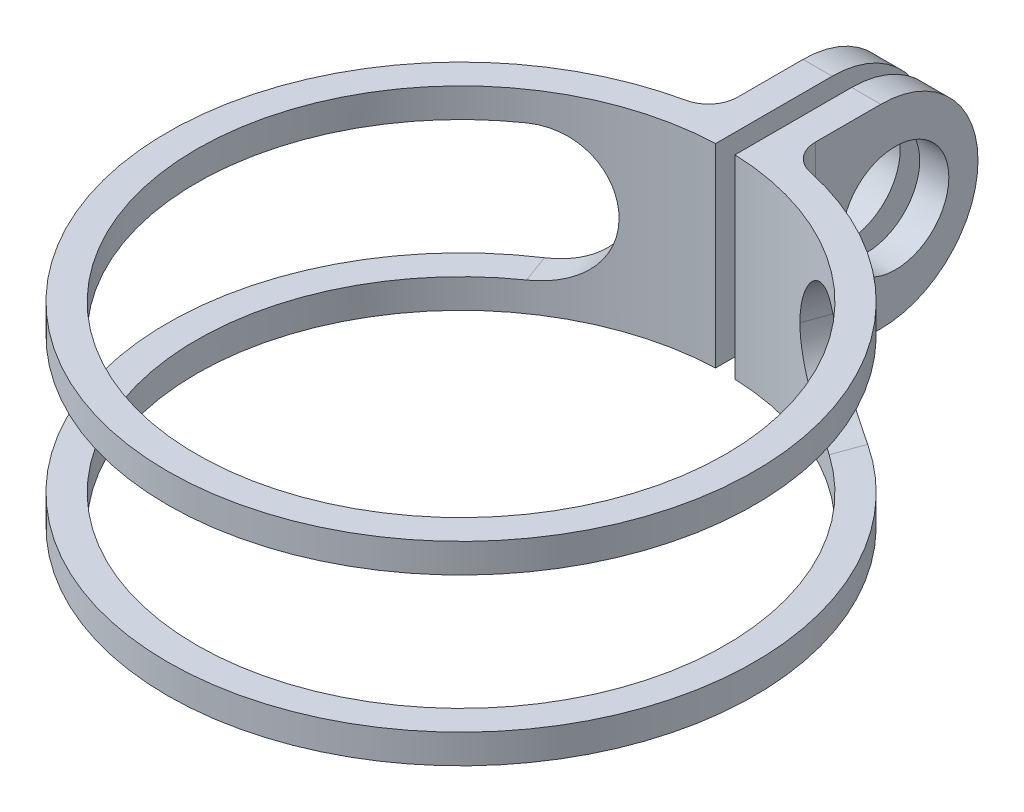
SolidWorks part; units mm, degrees
ref_plane "Front" through (0, 0, 0) normal (0, 0, 1) x (1, 0, 0)
ref_plane "Top" through (0, 0, 0) normal (0, 1, 0) x (1, 0, 0)
ref_plane "Right" through (0, 0, 0) normal (1, 0, 0) x (0, 0, -1)
sketch "Sketch1" plane through (0, 0, 0) normal (0, 1, 0) x (1, 0, 0)
  circle A0 centre (0, 0) radius 13.6
  dimension "D1" = 27.2
extrude "Extrude-Thin1" add sketch "Sketch1" along normal blind 10 thin thin type one direction wall 1.5
sketch "Sketch3" plane through (0, 0, 0) normal (0, 1, 0) x (1, 0, 0)
  line L0 (0, 0) -> (0, 11.9297) construction
  line L1 (-0.5, 11.9297) -> (0.5, 11.9297)
  line L2 (-0.5, 11.9297) -> (-0.5, 16.9297)
  line L3 (-0.5, 16.9297) -> (0.5, 16.9297)
  line L4 (0.5, 11.9297) -> (0.5, 16.9297)
  point P4 (0, 0)
  dimension "D1" = 1
  dimension "D2" = 5
extrude "Cut-Extrude2" cut sketch "Sketch3" along normal through all
sketch "Sketch4" plane through (0, 0, 0) normal (0, 1, 0) x (1, 0, 0)
  line L0 (-0.5, 13.5908) -> (-0.5, 24.5908)
  line L1 (-0.5, 24.5908) -> (-2, 24.5908)
  line L2 (-2, 24.5908) -> (-2, 13.5908)
  line L3 (-2, 13.5908) -> (-0.5, 13.5908)
  dimension "D1" = 1.5
  dimension "D2" = 11
extrude "Boss-Extrude1" add sketch "Sketch4" along normal blind 10
mirror "Mirror1" about plane through (0, 0, 0) normal (1, 0, 0) of "Boss-Extrude1"
sketch "Sketch5" plane through (0, 0, 0) normal (1, 0, 0) x (0, 0, -1)
  line L0 (24.5908, 5) -> (14.967, 5) construction
  line L1 (24.5908, 10) -> (24.5908, 0) construction
  line L2 (14.967, 0) -> (14.967, 10) construction
  circle A0 centre (20.3408, 5) radius 2.75
  circle A1 centre (20.3408, 5) radius 4.25 construction
  point P8 (20.2667, 5)
  dimension "D1" = 5.5
  dimension "D2" = 8.5
extrude "Cut-Extrude3" cut sketch "Sketch5" against normal through all and the other way through all
fillet "Fillet1" radius 1.5 2 edges at (-2, 5, -14.967) (2, 5, -14.967)
sketch "Sketch6" plane through (0, 0, 0) normal (1, 0, 0) x (0, 0, -1)
  line L0 (-3.5512, 5) -> (-22.5236, 5) construction
  line L1 (-3.5512, 1.5) -> (-22.5236, 1.5)
  line L2 (-3.5512, 8.5) -> (-22.5236, 8.5)
  line L4 (0, 10) -> (0, 0) construction
  line L5 (13.5908, 10) -> (-13.6, 10) construction
  line L6 (-15.1, 0) -> (14.7605, 0) construction
  line L8 (-3.5512, 8.5) -> (-3.5512, 1.5)
  line L9 (-22.5236, 8.5) -> (-22.5236, 1.5)
  point P2 (-14.4642, 5)
  point P7 (0, 5)
  dimension "D1" = 1.5
fillet "Fillet2" radius 5 4 edges at (1.25, 0, -24.5908) (-1.25, 0, -24.5908) (-1.25, 10, -24.5908) (1.25, 10, -24.5908)
revolve "Cut-Revolve1" cut sketch "Sketch6" angle 160 about L4 other way angle 160
fillet "Fillet3" radius 3.5 4 edges at (-4.908, 8.5, -13.4846) (-4.908, 1.5, -13.4846) (4.908, 1.5, -13.4846) (4.908, 8.5, -13.4846)
